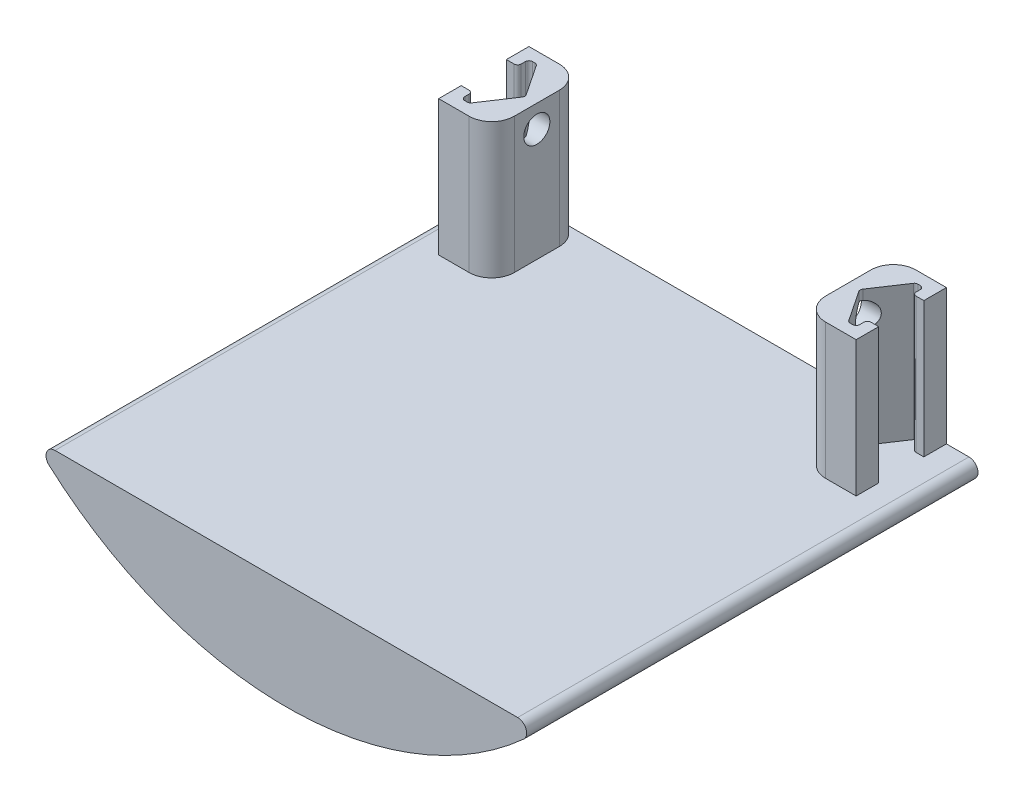
SolidWorks part; units mm, degrees
ref_plane "Front Plane" through (0, 0, 0) normal (0, 0, 1) x (1, 0, 0)
ref_plane "Top Plane" through (0, 0, 0) normal (0, 1, 0) x (1, 0, 0)
ref_plane "Right Plane" through (0, 0, 0) normal (1, 0, 0) x (0, 0, -1)
sketch "Sketch1" plane through (0, 0, 0) normal (0, 0, 1) x (1, 0, 0)
  line L0 (0, 1159.1945) -> (0, -70) construction
  line L1 (-71.4143, -70) -> (71.4143, -70)
  line L13 (0, -70) -> (0, -1062.27) construction
  arc A0 (-71.4143, -70) -> (71.4143, -70) centre (0, 0) ccw
  point P12 (0, -100)
  point P21 (0, -70)
  dimension "D1" = 200
  dimension "D6" = 30
extrude "Boss-Extrude1" add sketch "Sketch1" along normal blind 127
fillet "Fillet1" radius 2.54 2 edges at (-71.4143, -70, 63.5) (71.4143, -70, 63.5)
sketch "Sketch2" plane through (0, -70, 0) normal (0, 1, 0) x (1, 0, 0)
  line L0 (-58.7376, -6.35) -> (-58.7376, 0)
  line L1 (-58.7376, 0) -> (-43.8151, 0)
  line L2 (-43.8151, 0) -> (-43.8151, -25.4)
  line L3 (-43.8151, -25.4) -> (-58.7376, -25.4)
  line L4 (-58.7376, -25.4) -> (-58.7376, -19.05)
  line L5 (-58.7376, -19.05) -> (-55.5626, -19.05)
  line L6 (-55.5626, -19.05) -> (-55.5626, -22.225)
  line L7 (-55.5626, -22.225) -> (-53.3401, -22.225)
  line L8 (-53.3401, -22.225) -> (-46.9901, -12.7)
  line L9 (-46.9901, -12.7) -> (-53.3401, -3.175)
  line L10 (-53.3401, -3.175) -> (-55.5626, -3.175)
  line L11 (-55.5626, -3.175) -> (-55.5626, -6.35)
  line L12 (-55.5626, -6.35) -> (-58.7376, -6.35)
  line L13 (-58.7376, -12.7) -> (-43.8151, -12.7) construction
  line L14 (65.0876, 0) -> (-65.0876, 0) construction
  line L15 (-65.0876, 0) -> (-65.0876, -127) construction
  dimension "D1" = 12.7
  dimension "D2" = 25.4
  dimension "D3" = 3.175
  dimension "D4" = 19.05
  dimension "D5" = 3.175
  dimension "D6" = 2.2225
  dimension "D7" = 6.35
  dimension "D8" = 6.35
extrude "Boss-Extrude2" add sketch "Sketch2" along normal blind 38.1
mirror "Mirror1" about plane through (0, 0, 0) normal (1, 0, 0) of "Boss-Extrude2"
sketch "Sketch4" plane through (0, 0, 0) normal (1, 0, 0) x (0, 0, -1)
  line L0 (-12.7, -31.9) -> (-12.7, -70) construction
  line L1 (-12.7, -31.9) -> (-22.225, -31.9) construction
  circle A0 centre (-12.7, -38.25) radius 3.675
  dimension "D1" = 7.35
  dimension "D2" = 6.35
extrude "Cut-Extrude1" cut sketch "Sketch4" against normal through all both and the other way through all
fillet "Fillet2" radius 1 16 edges at (55.5626, -50.95, 3.175) (53.3401, -50.95, 3.175) (55.5626, -50.95, 19.05) (55.5626, -50.95, 6.35) (46.9901, -33.2375, 12.7) (46.9901, -55.9625, 12.7) (53.3401, -50.95, 22.225) (55.5626, -50.95, 22.225) (-53.3401, -50.95, 22.225) (-55.5626, -50.95, 19.05) (-55.5626, -50.95, 22.225) (-46.9901, -55.9625, 12.7) (-46.9901, -33.2375, 12.7) (-53.3401, -50.95, 3.175) (-55.5626, -50.95, 3.175) (-55.5626, -50.95, 6.35)
fillet "Fillet3" radius 6.35 4 edges at (43.8151, -50.95, 0) (43.8151, -50.95, 25.4) (-43.8151, -50.95, 0) (-43.8151, -50.95, 25.4)
